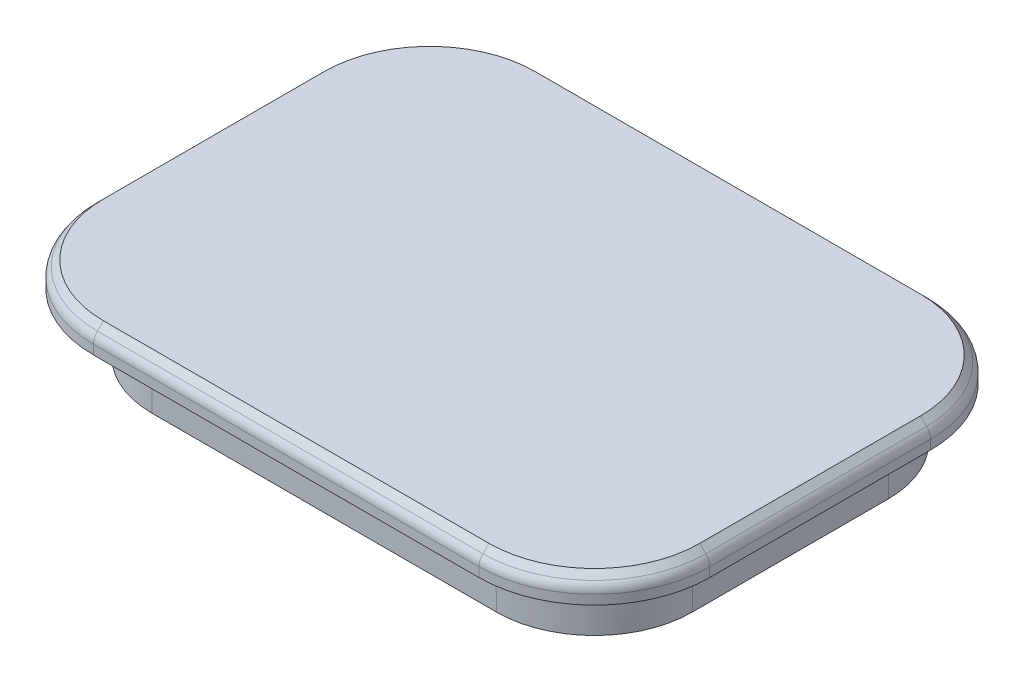
SolidWorks part; units mm, degrees
ref_plane "Front" through (0, 0, 0) normal (0, 0, 1) x (1, 0, 0)
ref_plane "Top" through (0, 0, 0) normal (0, 1, 0) x (1, 0, 0)
ref_plane "Right" through (0, 0, 0) normal (1, 0, 0) x (0, 0, -1)
sketch "Sketch1" plane through (0, 0, 0) normal (0, 1, 0) x (1, 0, 0)
  line L1 (6, 0) -> (26.9, 0)
  line L2 (0, 6) -> (0, 17.9)
  line L3 (6, 23.9) -> (26.9, 23.9)
  line L4 (32.9, 6) -> (32.9, 17.9)
  arc A0 (6, 0) -> (0, 6) centre (6, 6) cw
  arc A1 (26.9, 0) -> (32.9, 6) centre (26.9, 6) ccw
  arc A2 (26.9, 23.9) -> (32.9, 17.9) centre (26.9, 17.9) cw
  arc A3 (0, 17.9) -> (6, 23.9) centre (6, 17.9) cw
  point P7 (0, 0)
  point P10 (32.9, 0)
  point P13 (32.9, 23.9)
  point P16 (0, 23.9)
  dimension "D3" = 6
  dimension "D1" = 32.9
  dimension "D2" = 23.9
extrude "Boss-Extrude1" add sketch "Sketch1" along normal blind 3.6
sketch "Sketch2" plane through (0, 3.6, 0) normal (0, 1, 0) x (1, 0, 0)
  line L0 (0, 17.9) -> (0, 6) construction
  line L1 (4.75, 25.15) -> (28.15, 25.15)
  line L2 (-2.25, 18.15) -> (-2.25, 4.75)
  line L3 (4.75, -2.25) -> (28.15, -2.25)
  line L4 (35.15, 18.15) -> (35.15, 4.75)
  line L5 (26.9, 23.9) -> (6, 23.9) construction
  line L6 (32.9, 6) -> (32.9, 17.9) construction
  line L7 (6, 0) -> (26.9, 0) construction
  arc A0 (-2.25, 4.75) -> (4.75, -2.25) centre (4.75, 4.75) ccw
  arc A1 (28.15, -2.25) -> (35.15, 4.75) centre (28.15, 4.75) ccw
  arc A2 (28.15, 25.15) -> (35.15, 18.15) centre (28.15, 18.15) cw
  arc A3 (4.75, 25.15) -> (-2.25, 18.15) centre (4.75, 18.15) ccw
  dimension "D5" = 7
  dimension "D1" = 2.25
  dimension "D2" = 1.25
  dimension "D3" = 2.25
  dimension "D4" = 2.25
extrude "Boss-Extrude2" add sketch "Sketch2" along normal blind 1.5
sketch "Sketch3" plane through (0, 0, 0) normal (0, -1, 0) x (1, 0, 0)
  line L0 (26.9, -23.9) -> (6, -23.9) construction
  line L1 (25.7, -22.7) -> (7.2, -22.7)
  line L2 (31.7, -16.7) -> (31.7, -7.2)
  line L3 (25.7, -1.2) -> (7.2, -1.2)
  line L4 (1.2, -16.7) -> (1.2, -7.2)
  line L5 (32.9, -6) -> (32.9, -17.9) construction
  line L6 (6, 0) -> (26.9, 0) construction
  line L7 (0, -17.9) -> (0, -6) construction
  arc A0 (7.2, -22.7) -> (1.2, -16.7) centre (7.2, -16.7) cw
  arc A1 (7.2, -1.2) -> (1.2, -7.2) centre (7.2, -7.2) ccw
  arc A2 (31.7, -7.2) -> (25.7, -1.2) centre (25.7, -7.2) ccw
  arc A3 (25.7, -22.7) -> (31.7, -16.7) centre (25.7, -16.7) ccw
  dimension "D5" = 6
  dimension "D1" = 1.2
  dimension "D2" = 1.2
  dimension "D3" = 1.2
  dimension "D4" = 1.2
extrude "Cut-Extrude1" cut sketch "Sketch3" against normal blind 3.6
sketch "Sketch5" plane through (0, 3.6, 0) normal (0, -1, 0) x (1, 0, 0)
  line L0 (7.2, -22.7) -> (25.7, -22.7) construction
  line L1 (7.2, -1.2) -> (8.4, -1.2)
  line L2 (7.2, -1.2) -> (7.2, -6.2)
  line L3 (7.2, -22.7) -> (8.4, -22.7)
  line L4 (8.4, -1.2) -> (8.4, -6.2)
  line L5 (1.2, -7.2) -> (1.2, -16.7) construction
  line L6 (25.7, -1.2) -> (24.5, -1.2)
  line L7 (25.7, -1.2) -> (25.7, -6.2)
  line L8 (25.7, -22.7) -> (24.5, -22.7)
  line L9 (24.5, -1.2) -> (24.5, -6.2)
  line L10 (31.7, -16.7) -> (26.7, -16.7)
  line L11 (31.7, -16.7) -> (31.7, -15.5)
  line L12 (31.7, -15.5) -> (26.7, -15.5)
  line L13 (1.2, -16.7) -> (1.2, -15.5)
  line L14 (31.7, -16.7) -> (31.7, -7.2) construction
  line L15 (1.2, -7.2) -> (6.2, -7.2)
  line L16 (1.2, -7.2) -> (1.2, -8.4)
  line L17 (1.2, -8.4) -> (6.2, -8.4)
  line L18 (31.7, -7.2) -> (31.7, -8.4)
  line L19 (9.4, -7.2) -> (23.5, -7.2)
  line L20 (7.2, -9.4) -> (7.2, -14.5)
  line L21 (9.4, -8.4) -> (23.5, -8.4)
  line L22 (8.4, -9.4) -> (8.4, -14.5)
  line L23 (24.5, -9.4) -> (24.5, -14.5)
  line L24 (25.7, -9.4) -> (25.7, -14.5)
  line L25 (26.7, -7.2) -> (31.7, -7.2)
  line L26 (26.7, -8.4) -> (31.7, -8.4)
  line L27 (23.5, -15.5) -> (9.4, -15.5)
  line L28 (23.5, -16.7) -> (9.4, -16.7)
  line L29 (24.5, -17.7) -> (24.5, -22.7)
  line L30 (25.7, -17.7) -> (25.7, -22.7)
  line L31 (7.2, -17.7) -> (7.2, -22.7)
  line L32 (6.2, -15.5) -> (1.2, -15.5)
  line L33 (8.4, -17.7) -> (8.4, -22.7)
  line L34 (6.2, -16.7) -> (1.2, -16.7)
  arc A0 (23.5, -16.7) -> (24.5, -17.7) centre (23.5, -17.7) cw
  arc A1 (26.7, -16.7) -> (25.7, -17.7) centre (26.7, -17.7) ccw
  arc A2 (26.7, -15.5) -> (25.7, -14.5) centre (26.7, -14.5) cw
  arc A3 (23.5, -15.5) -> (24.5, -14.5) centre (23.5, -14.5) ccw
  arc A4 (25.7, -6.2) -> (26.7, -7.2) centre (26.7, -6.2) ccw
  arc A5 (25.7, -9.4) -> (26.7, -8.4) centre (26.7, -9.4) cw
  arc A6 (24.5, -9.4) -> (23.5, -8.4) centre (23.5, -9.4) ccw
  arc A7 (24.5, -6.2) -> (23.5, -7.2) centre (23.5, -6.2) cw
  arc A8 (9.4, -15.5) -> (8.4, -14.5) centre (9.4, -14.5) cw
  arc A9 (8.4, -17.7) -> (9.4, -16.7) centre (9.4, -17.7) cw
  arc A10 (7.2, -17.7) -> (6.2, -16.7) centre (6.2, -17.7) ccw
  arc A11 (7.2, -14.5) -> (6.2, -15.5) centre (6.2, -14.5) cw
  arc A12 (7.2, -9.4) -> (6.2, -8.4) centre (6.2, -9.4) ccw
  arc A13 (9.4, -8.4) -> (8.4, -9.4) centre (9.4, -9.4) ccw
  arc A14 (9.4, -7.2) -> (8.4, -6.2) centre (9.4, -6.2) cw
  arc A15 (6.2, -7.2) -> (7.2, -6.2) centre (6.2, -6.2) ccw
  point P44 (24.5, -16.7)
  point P47 (25.7, -16.7)
  point P54 (25.7, -7.2)
  point P57 (25.7, -8.4)
  point P68 (7.2, -16.7)
  point P71 (7.2, -15.5)
  point P76 (8.4, -8.4)
  dimension "D5" = 1
  dimension "D1" = 1.2
  dimension "D2" = 1.2
  dimension "D3" = 1.2
  dimension "D4" = 1.2
extrude "Boss-Extrude5" add sketch "Sketch5" along normal blind 3.6
chamfer "Chamfer1" distance 3.6 angle 1 8 edges at (0, 0, -11.95) (1.7574, 0, -1.7574) (1.7574, 0, -22.1426) (16.45, 0, 0) (16.45, 0, -23.9) (31.1426, 0, -1.7574) (31.1426, 0, -22.1426) (32.9, 0, -11.95) first distance on face at (0, 1.8, -11.95) first distance on face at (2.3787, 1.8, -2.3787) first distance on face at (2.3787, 1.8, -21.5213) first distance on face at (16.45, 1.8, 0) first distance on face at (16.45, 1.8, -23.9) first distance on face at (30.5213, 1.8, -2.3787) first distance on face at (30.5213, 1.8, -21.5213) first distance on face at (32.9, 1.8, -11.95)
fillet "Fillet3" radius 1 16 edges at (1.2, 1.8, -16.7) (1.2, 1.8, -8.4) (31.7, 1.8, -8.4) (24.5, 1.8, -1.2) (24.5, 1.8, -22.7) (25.7, 1.8, -1.2) (8.4, 1.8, -1.2) (7.2, 1.8, -1.2) (31.7, 1.8, -16.7) (31.7, 1.8, -7.2) (31.7, 1.8, -15.5) (7.2, 1.8, -22.7) (1.2, 1.8, -7.2) (1.2, 1.8, -15.5) (8.4, 1.8, -22.7) (25.7, 1.8, -22.7)
chamfer "Chamfer2" distance 0.6 angle 45 8 edges at (16.45, 5.1, -25.15) (-0.1997, 5.1, -23.0997) (33.0997, 5.1, -23.0997) (-2.25, 5.1, -11.45) (35.15, 5.1, -11.45) (-0.1997, 5.1, 0.1997) (33.0997, 5.1, 0.1997) (16.45, 5.1, 2.25)
fillet "Fillet4" radius 0.8 8 edges at (33.0997, 4.5, 0.1997) (35.15, 4.5, -11.45) (33.0997, 4.5, -23.0997) (16.45, 4.5, -25.15) (-0.1997, 4.5, -23.0997) (-2.25, 4.5, -11.45) (-0.1997, 4.5, 0.1997) (16.45, 4.5, 2.25)
